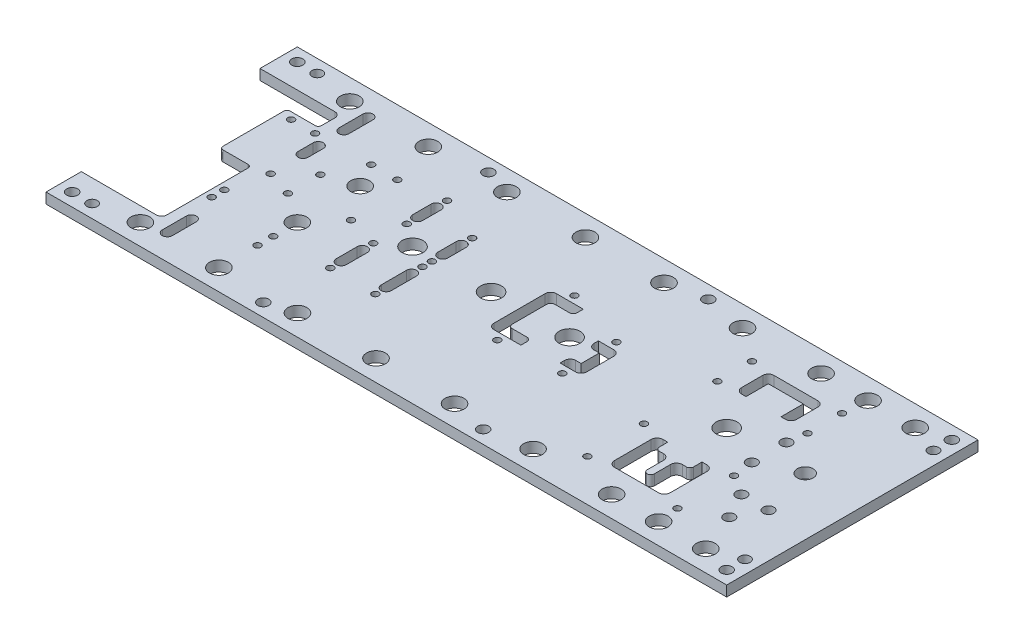
SolidWorks part; units mm, degrees
material "K110"
ref_plane "Front Plane" through (0, 0, 0) normal (0, 0, 1) x (1, 0, 0)
ref_plane "Top Plane" through (0, 0, 0) normal (0, 1, 0) x (1, 0, 0)
ref_plane "Right Plane" through (0, 0, 0) normal (1, 0, 0) x (0, 0, -1)
sketch "Sketch1" plane through (0, 0, 0) normal (0, 1, 0) x (1, 0, 0)
  line L1 (-325, -120) -> (325, -120)
  line L2 (-325, -120) -> (-325, 120)
  line L3 (-325, 120) -> (325, 120)
  line L4 (325, -120) -> (325, 120)
  line L5 (-325, -120) -> (325, 120) construction
  line L6 (-325, 120) -> (325, -120) construction
  point P0 (0, 0)
  dimension "D1" = 650
  dimension "D2" = 240
extrude "Boss-Extrude1" add sketch "Sketch1" against normal blind 10
sketch "Sketch2" plane through (0, -10, 0) normal (0, -1, 0) x (1, 0, 0)
  circle A0 centre (-254.87, 100) radius 9 construction
  circle A1 centre (-254.87, -100) radius 9
  circle A2 centre (-254.87, -100) radius 9
  circle A3 centre (285, -100) radius 9
  circle A4 centre (285, -100) radius 9
  circle A5 centre (120.13, 100) radius 9
  circle A6 centre (120.13, 100) radius 9
  circle A7 centre (120.13, -100) radius 9
  circle A8 centre (120.13, -100) radius 9
  circle A9 centre (45.13, 100) radius 9
  circle A10 centre (45.13, 100) radius 9
  circle A11 centre (240, 100) radius 9
  circle A12 centre (240, 100) radius 9
  circle A13 centre (240, -100) radius 9
  circle A14 centre (240, -100) radius 9
  circle A15 centre (195.13, -100) radius 9
  circle A16 centre (195.13, -100) radius 9
  circle A17 centre (285, 100) radius 9
  circle A18 centre (285, 100) radius 9
  circle A19 centre (-104.87, -100) radius 9
  circle A20 centre (-104.87, -100) radius 9
  circle A21 centre (-179.87, 100) radius 9
  circle A22 centre (-179.87, 100) radius 9
  circle A23 centre (-179.87, -100) radius 9
  circle A24 centre (-179.87, -100) radius 9
  circle A25 centre (45.13, -100) radius 9
  circle A26 centre (45.13, -100) radius 9
  circle A27 centre (-29.87, 100) radius 9
  circle A28 centre (-29.87, 100) radius 9
  circle A29 centre (-29.87, -100) radius 9
  circle A30 centre (-29.87, -100) radius 9
  circle A31 centre (-104.87, 100) radius 9
  circle A32 centre (-104.87, 100) radius 9
  circle A33 centre (195.13, 100) radius 9
  circle A34 centre (195.13, 100) radius 9
  circle A35 centre (-254.87, 100) radius 9
  circle A36 centre (195.13, -9.86) radius 10 construction
  circle A37 centre (45.13, -9.86) radius 10 construction
  circle A38 centre (-29.87, -9.86) radius 10 construction
  circle A39 centre (-104.87, -9.86) radius 10 construction
  circle A40 centre (-179.87, 25.14) radius 9 construction
  circle A41 centre (-179.87, -34.86) radius 9 construction
  circle A42 centre (195.13, -9.86) radius 10
  circle A43 centre (45.13, -9.86) radius 10
  circle A44 centre (-29.87, -9.86) radius 10
  circle A45 centre (-104.87, -9.86) radius 10
  circle A46 centre (-179.87, 25.14) radius 9
  circle A47 centre (-179.87, -34.86) radius 9
  dimension "D1" = 0
  dimension "D2" = 0
  dimension "D3" = 0
  dimension "D4" = 0
  dimension "D5" = 0
  dimension "D6" = 0
  dimension "D7" = 0
  dimension "D8" = 0
  dimension "D9" = 0
  dimension "D10" = 0
  dimension "D11" = 0
  dimension "D12" = 0
  dimension "D13" = 0
  dimension "D14" = 0
  dimension "D15" = 0
  dimension "D16" = 0
  dimension "D17" = 0
extrude "Cut-Extrude1" cut sketch "Sketch2" against normal up to next
hole_wizard "M6 Clearance Hole1" positions "Sketch7" profile "Sketch6" hole size "M6" standard "ISO" end condition through all
sketch "Sketch7" plane through (0, -10, 0) normal (0, -1, 0) x (-1, 0, 0)
  line L0 (232.87, -8.64) -> (232.87, 13.36) construction
  point P0 (-238.13, -26.14)
  point P3 (-152.13, -26.14)
  point P6 (-152.13, -80.14)
  point P9 (-238.13, -80.14)
  point P12 (-238.13, 77)
  point P15 (-152.13, 77)
  point P18 (-152.13, 44)
  point P21 (-238.13, 44)
  point P24 (-71.5, -23.4862)
  point P27 (-71.5, 28.2062)
  point P30 (-12.94, -26.9862)
  point P33 (-12.94, 46.7062)
  point P36 (83.37, 45.36)
  point P39 (83.37, 6.86)
  point P42 (126.37, 25.86)
  point P45 (126.37, 64.36)
  point P48 (83.37, -2.14)
  point P51 (126.37, -6.14)
  point P54 (126.37, -47.14)
  point P57 (83.37, -47.14)
  point P60 (156.12, 2.36)
  point P63 (208.37, -5.64)
  point P66 (208.37, 25.36)
  point P69 (192.37, 57.86)
  point P72 (167.37, 57.86)
  point P75 (179.87, -48.14)
  point P78 (179.87, -63.14)
  point P81 (241.62, -33.14)
  point P84 (241.62, -45.14)
  point P87 (232.87, 2.36)
  point P91 (267.87, 56.92)
  point P94 (245.0007, 56.92)
sketch "Sketch6" plane through (238.13, -10, 26.14) normal (1, 0, 0) x (0, 0, -1)
  line L0 (0, 0) -> (0, 10)
  line L1 (0, 10) -> (3.2, 10)
  line L2 (3.2, 10) -> (3.2, 0.025)
  line L3 (3.2, 0.025) -> (3.225, 0)
  line L5 (3.225, 0) -> (0, 0)
  line L6 (-3.2, 0.025) -> (-3.225, 0) construction
  line L11 (0, -6.35) -> (0, 107.95) construction
  dimension "Thru Hole Dia." = 6.4
  dimension "Thru Hole Depth" = 10
  dimension "Near C'Sink Dia." = 6.45
  dimension "Near C'Sink Angle" = 90
sketch "Sketch8" plane through (0, 0, 0) normal (0, 1, 0) x (1, 0, 0)
  line L0 (-325, -86.2624) -> (-253.37, -86.2624) construction
  line L2 (-248.37, -52.14) -> (-248.37, -14.64) construction
  line L3 (-278.37, 33.36) -> (-278.37, 2.36) construction
  line L4 (-248.37, 63.475) -> (-248.37, 79.36) construction
  line L5 (-253.37, 84.36) -> (-325, 84.36) construction
  line L6 (-325, -86.2624) -> (-253.37, -86.2624)
  line L8 (-248.37, -81.2624) -> (-248.37, -3.64)
  line L9 (-278.37, 63.48) -> (-278.37, 2.36)
  line L10 (-248.37, 63.48) -> (-248.37, 79.36)
  line L11 (-253.37, 84.36) -> (-325, 84.36)
  line L12 (-273.87, 63.48) -> (-237.87, 63.48) construction
  line L13 (-278.37, 63.48) -> (-248.37, 63.48)
  line L14 (-325, 84.36) -> (-325, -86.2624)
  line L17 (-251.37, -0.64) -> (-270.37, -0.64) construction
  line L18 (-251.37, -0.64) -> (-275.37, -0.64)
  arc A0 (-253.37, -86.2624) -> (-248.37, -81.2624) centre (-253.37, -81.2624) ccw construction
  arc A1 (-248.37, 79.36) -> (-253.37, 84.36) centre (-253.37, 79.36) ccw construction
  arc A2 (-253.37, -86.2624) -> (-248.37, -81.2624) centre (-253.37, -81.2624) ccw
  arc A3 (-248.37, 79.36) -> (-253.37, 84.36) centre (-253.37, 79.36) ccw
  arc A4 (-248.37, -3.64) -> (-251.37, -0.64) centre (-251.37, -3.64) ccw construction
  arc A5 (-248.37, -3.64) -> (-251.37, -0.64) centre (-251.37, -3.64) ccw
  arc A6 (-278.37, 2.36) -> (-275.37, -0.64) centre (-275.37, 2.36) ccw construction
  arc A7 (-278.37, 2.36) -> (-275.37, -0.64) centre (-275.37, 2.36) ccw
extrude "Cut-Extrude2" cut sketch "Sketch8" against normal up to next
fillet "Fillet1" radius 3 2 edges at (-248.37, -5, -63.48) (-278.37, -5, -63.48)
sketch "Sketch12" plane through (0, -10, 0) normal (0, -1, 0) x (1, 0, 0)
  line L18 (211.8377, -45.0677) -> (211.8377, -66.3477)
  line L19 (178.4223, -66.3477) -> (178.4223, -45.0677)
  line L20 (211.8377, -66.3477) -> (178.4223, -66.3477)
  line L21 (216.13, -45.0677) -> (211.8377, -45.0677)
  line L22 (221.4223, -70.64) -> (221.4223, -50.36)
  line L23 (195.13, -75.9323) -> (216.13, -75.9323)
  line L24 (174.13, -75.9323) -> (195.13, -75.9323)
  line L25 (178.4223, -45.0677) -> (174.13, -45.0677)
  line L26 (168.8377, -50.36) -> (168.8377, -70.64)
  line L27 (211.8377, -45.0677) -> (211.8377, -66.3477)
  line L28 (178.4223, -66.3477) -> (178.4223, -45.0677)
  line L29 (211.8377, -66.3477) -> (178.4223, -66.3477)
  line L30 (216.13, -45.0677) -> (211.8377, -45.0677)
  line L31 (221.4223, -70.64) -> (221.4223, -50.36)
  line L32 (195.13, -75.9323) -> (216.13, -75.9323)
  line L33 (174.13, -75.9323) -> (195.13, -75.9323)
  line L34 (178.4223, -45.0677) -> (174.13, -45.0677)
  line L35 (168.8377, -50.36) -> (168.8377, -70.64)
  line L51 (211.5164, 30.0264) -> (216.13, 30.0264)
  line L52 (221.7436, 35.64) -> (221.7436, 53.14)
  line L53 (221.7436, 53.14) -> (221.7436, 70.64)
  line L54 (216.13, 76.2536) -> (174.13, 76.2536)
  line L55 (168.5164, 70.64) -> (168.5164, 35.64)
  line L56 (174.13, 30.0264) -> (178.7436, 30.0264)
  line L57 (211.5164, 38.14) -> (211.5164, 30.0264)
  line L58 (204.13, 41.5264) -> (208.13, 41.5264)
  line L59 (198.5164, 62.64) -> (198.5164, 47.14)
  line L60 (191.7436, 47.14) -> (191.7436, 62.64)
  line L61 (182.13, 41.5264) -> (186.13, 41.5264)
  line L62 (178.7436, 30.0264) -> (178.7436, 38.14)
  line L63 (211.5164, 30.0264) -> (216.13, 30.0264)
  line L64 (221.7436, 35.64) -> (221.7436, 53.14)
  line L65 (221.7436, 53.14) -> (221.7436, 70.64)
  line L66 (216.13, 76.2536) -> (174.13, 76.2536)
  line L67 (168.5164, 70.64) -> (168.5164, 35.64)
  line L68 (174.13, 30.0264) -> (178.7436, 30.0264)
  line L69 (211.5164, 38.14) -> (211.5164, 30.0264)
  line L70 (204.13, 41.5264) -> (208.13, 41.5264)
  line L71 (198.5164, 62.64) -> (198.5164, 47.14)
  line L72 (191.7436, 47.14) -> (191.7436, 62.64)
  line L73 (182.13, 41.5264) -> (186.13, 41.5264)
  line L74 (178.7436, 30.0264) -> (178.7436, 38.14)
  arc A8 (221.4223, -50.36) -> (216.13, -45.0677) centre (216.13, -50.36) ccw
  arc A9 (216.13, -75.9323) -> (221.4223, -70.64) centre (216.13, -70.64) ccw
  arc A10 (174.13, -45.0677) -> (168.8377, -50.36) centre (174.13, -50.36) ccw
  arc A11 (168.8377, -70.64) -> (174.13, -75.9323) centre (174.13, -70.64) ccw
  arc A12 (221.4223, -50.36) -> (216.13, -45.0677) centre (216.13, -50.36) ccw
  arc A13 (216.13, -75.9323) -> (221.4223, -70.64) centre (216.13, -70.64) ccw
  arc A14 (174.13, -45.0677) -> (168.8377, -50.36) centre (174.13, -50.36) ccw
  arc A15 (168.8377, -70.64) -> (174.13, -75.9323) centre (174.13, -70.64) ccw
  arc A30 (216.13, 30.0264) -> (221.7436, 35.64) centre (216.13, 35.64) ccw
  arc A31 (221.7436, 70.64) -> (216.13, 76.2536) centre (216.13, 70.64) ccw
  arc A32 (174.13, 76.2536) -> (168.5164, 70.64) centre (174.13, 70.64) ccw
  arc A33 (168.5164, 35.64) -> (174.13, 30.0264) centre (174.13, 35.64) ccw
  arc A34 (211.5164, 38.14) -> (208.13, 41.5264) centre (208.13, 38.14) ccw
  arc A35 (198.5164, 47.14) -> (204.13, 41.5264) centre (204.13, 47.14) ccw
  arc A36 (198.5164, 62.64) -> (191.7436, 62.64) centre (195.13, 62.64) ccw
  arc A37 (186.13, 41.5264) -> (191.7436, 47.14) centre (186.13, 47.14) ccw
  arc A38 (182.13, 41.5264) -> (178.7436, 38.14) centre (182.13, 38.14) ccw
  arc A39 (216.13, 30.0264) -> (221.7436, 35.64) centre (216.13, 35.64) ccw
  arc A40 (221.7436, 70.64) -> (216.13, 76.2536) centre (216.13, 70.64) ccw
  arc A41 (174.13, 76.2536) -> (168.5164, 70.64) centre (174.13, 70.64) ccw
  arc A42 (168.5164, 35.64) -> (174.13, 30.0264) centre (174.13, 35.64) ccw
  arc A43 (211.5164, 38.14) -> (208.13, 41.5264) centre (208.13, 38.14) ccw
  arc A44 (198.5164, 47.14) -> (204.13, 41.5264) centre (204.13, 47.14) ccw
  arc A45 (198.5164, 62.64) -> (191.7436, 62.64) centre (195.13, 62.64) ccw
  arc A46 (186.13, 41.5264) -> (191.7436, 47.14) centre (186.13, 47.14) ccw
  arc A47 (182.13, 41.5264) -> (178.7436, 38.14) centre (182.13, 38.14) ccw
  circle A1945 centre (270.13, 62.64) radius 5.1136
  circle A1946 centre (270.13, 62.64) radius 5.1136
  circle A1948 centre (283.13, 38.14) radius 5.1136
  circle A1949 centre (283.13, 38.14) radius 5.1136
  circle A1951 centre (257.13, 38.14) radius 5.1136
  circle A1952 centre (257.13, 38.14) radius 5.1136
  circle A1954 centre (270.13, -9.86) radius 7.6136
  circle A1955 centre (270.13, -9.86) radius 7.6136
  circle A1957 centre (235.63, -26.36) radius 5.1136
  circle A1958 centre (235.63, -26.36) radius 5.1136
  circle A1960 centre (235.63, 6.64) radius 5.1136
  circle A1961 centre (235.63, 6.64) radius 5.1136
  dimension "D1" = 1.6
  dimension "D2" = 1.6
  dimension "D3" = 1.6
  dimension "D4" = 1.6
  dimension "D5" = 1.6
  dimension "D6" = 1.6
  dimension "D7" = 1.6
  dimension "D8" = 1.6
extrude "Cut-Extrude3" cut sketch "Sketch12" against normal up to next
sketch "Sketch13" plane through (0, -10, 0) normal (0, -1, 0) x (1, 0, 0)
  line L72 (61.8377, 15.9323) -> (61.8377, 11.64)
  line L73 (67.13, 6.3477) -> (72.3377, 6.3477)
  line L74 (72.3377, 6.3477) -> (72.3377, -11.0677)
  line L75 (72.3377, -11.0677) -> (67.13, -11.0677)
  line L76 (61.8377, -16.36) -> (61.8377, -20.6523)
  line L77 (76.63, 15.9323) -> (61.8377, 15.9323)
  line L78 (81.9223, -2.36) -> (81.9223, 10.64)
  line L79 (81.9223, -15.36) -> (81.9223, -2.36)
  line L80 (61.8377, -20.6523) -> (76.63, -20.6523)
  line L81 (61.8377, 15.9323) -> (61.8377, 11.64)
  line L82 (67.13, 6.3477) -> (72.3377, 6.3477)
  line L83 (72.3377, 6.3477) -> (72.3377, -11.0677)
  line L84 (72.3377, -11.0677) -> (67.13, -11.0677)
  line L85 (61.8377, -16.36) -> (61.8377, -20.6523)
  line L86 (76.63, 15.9323) -> (61.8377, 15.9323)
  line L87 (81.9223, -2.36) -> (81.9223, 10.64)
  line L88 (81.9223, -15.36) -> (81.9223, -2.36)
  line L89 (61.8377, -20.6523) -> (76.63, -20.6523)
  line L99 (2.63, -39.6523) -> (28.4223, -39.6523)
  line L100 (-2.6623, -13.23) -> (-2.6623, -34.36)
  line L101 (-2.6623, 14.64) -> (-2.6623, -13.23)
  line L102 (28.4223, 19.9323) -> (2.63, 19.9323)
  line L103 (28.4223, 14.14) -> (28.4223, 19.9323)
  line L104 (28.4223, -39.6523) -> (28.4223, -33.86)
  line L105 (24.63, -30.0677) -> (10.63, -30.0677)
  line L106 (6.9223, -26.36) -> (6.9223, 6.64)
  line L107 (10.63, 10.3477) -> (24.63, 10.3477)
  line L108 (2.63, -39.6523) -> (28.4223, -39.6523)
  line L109 (-2.6623, -13.23) -> (-2.6623, -34.36)
  line L110 (-2.6623, 14.64) -> (-2.6623, -13.23)
  line L111 (28.4223, 19.9323) -> (2.63, 19.9323)
  line L112 (28.4223, 14.14) -> (28.4223, 19.9323)
  line L113 (28.4223, -39.6523) -> (28.4223, -33.86)
  line L114 (24.63, -30.0677) -> (10.63, -30.0677)
  line L115 (6.9223, -26.36) -> (6.9223, 6.64)
  line L116 (10.63, 10.3477) -> (24.63, 10.3477)
  arc A48 (61.8377, 11.64) -> (67.13, 6.3477) centre (67.13, 11.64) ccw
  arc A49 (67.13, -11.0677) -> (61.8377, -16.36) centre (67.13, -16.36) ccw
  arc A50 (81.9223, 10.64) -> (76.63, 15.9323) centre (76.63, 10.64) ccw
  arc A51 (76.63, -20.6523) -> (81.9223, -15.36) centre (76.63, -15.36) ccw
  arc A52 (61.8377, 11.64) -> (67.13, 6.3477) centre (67.13, 11.64) ccw
  arc A53 (67.13, -11.0677) -> (61.8377, -16.36) centre (67.13, -16.36) ccw
  arc A54 (81.9223, 10.64) -> (76.63, 15.9323) centre (76.63, 10.64) ccw
  arc A55 (76.63, -20.6523) -> (81.9223, -15.36) centre (76.63, -15.36) ccw
  arc A62 (-2.6623, -34.36) -> (2.63, -39.6523) centre (2.63, -34.36) ccw
  arc A63 (2.63, 19.9323) -> (-2.6623, 14.64) centre (2.63, 14.64) ccw
  arc A64 (28.4223, -33.86) -> (24.63, -30.0677) centre (24.63, -33.86) ccw
  arc A65 (6.9223, -26.36) -> (10.63, -30.0677) centre (10.63, -26.36) ccw
  arc A66 (10.63, 10.3477) -> (6.9223, 6.64) centre (10.63, 6.64) ccw
  arc A67 (24.63, 10.3477) -> (28.4223, 14.14) centre (24.63, 14.14) ccw
  arc A68 (-2.6623, -34.36) -> (2.63, -39.6523) centre (2.63, -34.36) ccw
  arc A69 (2.63, 19.9323) -> (-2.6623, 14.64) centre (2.63, 14.64) ccw
  arc A70 (28.4223, -33.86) -> (24.63, -30.0677) centre (24.63, -33.86) ccw
  arc A71 (6.9223, -26.36) -> (10.63, -30.0677) centre (10.63, -26.36) ccw
  arc A72 (10.63, 10.3477) -> (6.9223, 6.64) centre (10.63, 6.64) ccw
  arc A73 (24.63, 10.3477) -> (28.4223, 14.14) centre (24.63, 14.14) ccw
  dimension "D1" = 1.6
  dimension "D2" = 1.6
extrude "Cut-Extrude4" cut sketch "Sketch13" against normal up to next
sketch "Sketch14" plane through (0, -10, 0) normal (0, -1, 0) x (1, 0, 0)
  line L8 (-88.1623, -17.31) -> (-88.1623, -34.91)
  line L9 (-78.5777, -26.11) -> (-78.5777, -17.31)
  line L10 (-78.5777, -34.91) -> (-78.5777, -26.11)
  line L11 (-88.1623, -17.31) -> (-88.1623, -34.91)
  line L12 (-78.5777, -26.11) -> (-78.5777, -17.31)
  line L13 (-78.5777, -34.91) -> (-78.5777, -26.11)
  line L17 (-78.5777, 12.59) -> (-78.5777, 24.64)
  line L18 (-88.1623, 36.69) -> (-88.1623, 12.59)
  line L19 (-78.5777, 24.64) -> (-78.5777, 36.69)
  line L20 (-78.5777, 12.59) -> (-78.5777, 24.64)
  line L21 (-88.1623, 36.69) -> (-88.1623, 12.59)
  line L22 (-78.5777, 24.64) -> (-78.5777, 36.69)
  line L26 (-131.2322, 36.69) -> (-131.2322, 16.59)
  line L27 (-121.5078, 26.64) -> (-121.5078, 36.69)
  line L28 (-121.5078, 16.59) -> (-121.5078, 26.64)
  line L29 (-131.2322, 36.69) -> (-131.2322, 16.59)
  line L30 (-121.5078, 26.64) -> (-121.5078, 36.69)
  line L31 (-121.5078, 16.59) -> (-121.5078, 26.64)
  line L35 (-131.1623, -36.31) -> (-131.1623, -53.91)
  line L36 (-121.5777, -45.11) -> (-121.5777, -36.31)
  line L37 (-121.5777, -53.91) -> (-121.5777, -45.11)
  line L38 (-131.1623, -36.31) -> (-131.1623, -53.91)
  line L39 (-121.5777, -45.11) -> (-121.5777, -36.31)
  line L40 (-121.5777, -53.91) -> (-121.5777, -45.11)
  arc A6 (-88.1623, -34.91) -> (-78.5777, -34.91) centre (-83.37, -34.91) ccw
  arc A7 (-78.5777, -17.31) -> (-88.1623, -17.31) centre (-83.37, -17.31) ccw
  arc A8 (-88.1623, -34.91) -> (-78.5777, -34.91) centre (-83.37, -34.91) ccw
  arc A9 (-78.5777, -17.31) -> (-88.1623, -17.31) centre (-83.37, -17.31) ccw
  arc A12 (-88.1623, 12.59) -> (-78.5777, 12.59) centre (-83.37, 12.59) ccw
  arc A13 (-78.5777, 36.69) -> (-88.1623, 36.69) centre (-83.37, 36.69) ccw
  arc A14 (-88.1623, 12.59) -> (-78.5777, 12.59) centre (-83.37, 12.59) ccw
  arc A15 (-78.5777, 36.69) -> (-88.1623, 36.69) centre (-83.37, 36.69) ccw
  arc A18 (-131.2322, 16.59) -> (-121.5078, 16.59) centre (-126.37, 16.59) ccw
  arc A19 (-121.5078, 36.69) -> (-131.2322, 36.69) centre (-126.37, 36.69) ccw
  arc A20 (-131.2322, 16.59) -> (-121.5078, 16.59) centre (-126.37, 16.59) ccw
  arc A21 (-121.5078, 36.69) -> (-131.2322, 36.69) centre (-126.37, 36.69) ccw
  arc A24 (-131.1623, -53.91) -> (-121.5777, -53.91) centre (-126.37, -53.91) ccw
  arc A25 (-121.5777, -36.31) -> (-131.1623, -36.31) centre (-126.37, -36.31) ccw
  arc A26 (-131.1623, -53.91) -> (-121.5777, -53.91) centre (-126.37, -53.91) ccw
  arc A27 (-121.5777, -36.31) -> (-131.1623, -36.31) centre (-126.37, -36.31) ccw
  dimension "D1" = 1.6
  dimension "D2" = 1.6
  dimension "D3" = 1.6
  dimension "D4" = 1.6
extrude "Cut-Extrude5" cut sketch "Sketch14" against normal up to next
sketch "Sketch15" plane through (0, -10, 0) normal (0, -1, 0) x (1, 0, 0)
  line L6 (-228.5777, -95.77) -> (-228.5777, -84.32)
  line L7 (-228.5777, -84.32) -> (-228.5777, -72.87)
  line L8 (-238.1623, -72.87) -> (-238.1623, -95.77)
  line L9 (-228.5777, -95.77) -> (-228.5777, -84.32)
  line L10 (-228.5777, -84.32) -> (-228.5777, -72.87)
  line L11 (-238.1623, -72.87) -> (-238.1623, -95.77)
  line L15 (-238.1623, -33.86) -> (-238.1623, -48.36)
  line L16 (-228.5777, -41.11) -> (-228.5777, -33.86)
  line L17 (-228.5777, -48.36) -> (-228.5777, -41.11)
  line L18 (-238.1623, -33.86) -> (-238.1623, -48.36)
  line L19 (-228.5777, -41.11) -> (-228.5777, -33.86)
  line L20 (-228.5777, -48.36) -> (-228.5777, -41.11)
  line L24 (-238.1623, 95.77) -> (-238.1623, 72.87)
  line L25 (-228.5777, 84.32) -> (-228.5777, 95.77)
  line L26 (-228.5777, 72.87) -> (-228.5777, 84.32)
  line L27 (-238.1623, 95.77) -> (-238.1623, 72.87)
  line L28 (-228.5777, 84.32) -> (-228.5777, 95.77)
  line L29 (-228.5777, 72.87) -> (-228.5777, 84.32)
  arc A4 (-228.5777, -72.87) -> (-238.1623, -72.87) centre (-233.37, -72.87) ccw
  arc A5 (-238.1623, -95.77) -> (-228.5777, -95.77) centre (-233.37, -95.77) ccw
  arc A6 (-228.5777, -72.87) -> (-238.1623, -72.87) centre (-233.37, -72.87) ccw
  arc A7 (-238.1623, -95.77) -> (-228.5777, -95.77) centre (-233.37, -95.77) ccw
  arc A10 (-228.5777, -33.86) -> (-238.1623, -33.86) centre (-233.37, -33.86) ccw
  arc A11 (-238.1623, -48.36) -> (-228.5777, -48.36) centre (-233.37, -48.36) ccw
  arc A12 (-228.5777, -33.86) -> (-238.1623, -33.86) centre (-233.37, -33.86) ccw
  arc A13 (-238.1623, -48.36) -> (-228.5777, -48.36) centre (-233.37, -48.36) ccw
  arc A16 (-228.5777, 95.77) -> (-238.1623, 95.77) centre (-233.37, 95.77) ccw
  arc A17 (-238.1623, 72.87) -> (-228.5777, 72.87) centre (-233.37, 72.87) ccw
  arc A18 (-228.5777, 95.77) -> (-238.1623, 95.77) centre (-233.37, 95.77) ccw
  arc A19 (-238.1623, 72.87) -> (-228.5777, 72.87) centre (-233.37, 72.87) ccw
  dimension "D1" = 1.6
  dimension "D2" = 1.6
  dimension "D3" = 1.6
extrude "Cut-Extrude6" cut sketch "Sketch15" against normal up to next
hole_wizard "M10 Clearance Hole1" positions "Sketch28" profile "Sketch17" hole size "M10" standard "ISO" end condition through all
sketch "Sketch28" plane through (0, -10, 0) normal (0, -1, 0) x (-1, 0, 0)
  point P52 (-312.5, 107.5)
  point P55 (-312.5, -107.5)
  point P58 (-80, 107.5)
  point P61 (130, 107.5)
  point P64 (312.5, 107.5)
  point P67 (312.5, -107.5)
  point P70 (130, -107.5)
  point P73 (-80, -107.5)
sketch "Sketch17" plane through (312.5, -10, -107.5) normal (1, 0, 0) x (0, 0, -1)
  line L0 (0, 0) -> (0, 10)
  line L1 (0, 10) -> (5.25, 10)
  line L2 (5.25, 10) -> (5.25, 0)
  line L5 (5.25, 0) -> (0, 0)
  line L11 (0, -6.35) -> (0, 107.95) construction
  dimension "Thru Hole Dia." = 10.5
  dimension "Thru Hole Depth" = 10
hole_wizard "Ø10.0mm Dowel Hole1" positions "Sketch23" profile "Sketch21" hole size "Ø10.0" standard "ISO" end condition through all
sketch "Sketch23" plane through (0, -10, 0) normal (0, -1, 0) x (-1, 0, 0)
  point P0 (-312.5, 90)
  point P3 (-312.5, -90)
  point P6 (293.5, -107.5)
  point P9 (293.5, 107.5)
sketch "Sketch21" plane through (312.5, -10, -90) normal (1, 0, 0) x (0, 0, -1)
  line L0 (0, 0) -> (0, 10)
  line L1 (0, 10) -> (5, 10)
  line L2 (5, 10) -> (5, 0)
  line L5 (5, 0) -> (0, 0)
  line L11 (0, -6.35) -> (0, 107.95) construction
  dimension "Thru Hole Dia." = 10
  dimension "Thru Hole Depth" = 10
